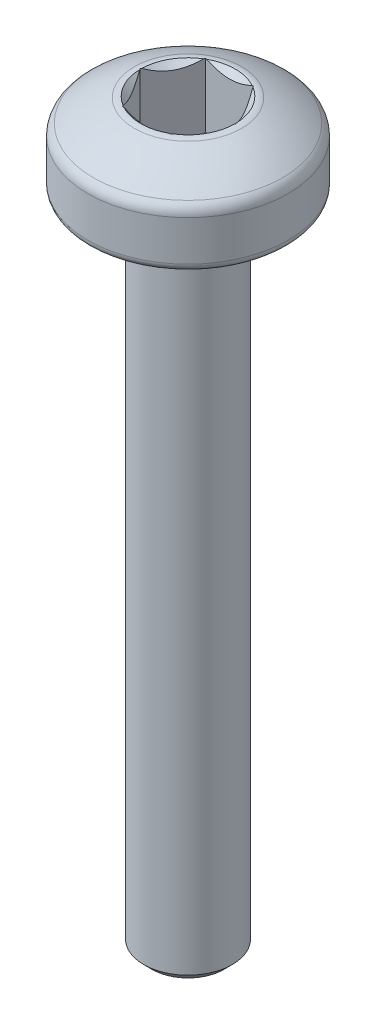
SolidWorks part; units mm, degrees
ref_plane "Front" through (0, 0, 0) normal (0, 0, 1) x (1, 0, 0)
ref_plane "Top" through (0, 0, 0) normal (0, 1, 0) x (1, 0, 0)
ref_plane "Right" through (0, 0, 0) normal (1, 0, 0) x (0, 0, -1)
sketch "Sketch1" plane through (0, 0, 0) normal (1, 0, 0) x (0, 0, -1)
  line L0 (0, 13.5) -> (0, 0) construction
  line L1 (0, 0) -> (7.1673, 0) construction
  line L2 (0, 13.5) -> (-2.498, 13.5) construction
  line L3 (0.95, 11.85) -> (1.66, 11.85)
  line L4 (0.8, 11.7) -> (0.8, 0.15)
  line L5 (0.8, 0.15) -> (0.65, 0)
  line L6 (0.65, 0) -> (0, 0)
  line L7 (0, 0) -> (0, 12)
  line L8 (1.81, 12) -> (1.81, 12.7288)
  line L9 (0.725, 13.22) -> (0.725, 12.2969)
  line L10 (0.725, 13.22) -> (0.855, 13.35)
  line L11 (0.875, 13.3494) -> (0.875, 12.2562)
  arc A0 (0.95, 11.85) -> (0.8, 11.7) centre (0.95, 11.7) ccw
  arc A1 (1.66, 11.85) -> (1.81, 12) centre (1.66, 12) ccw
  arc A2 (0, 12) -> (0.768, 12.1125) centre (0, 14.6781) ccw
  arc A3 (0.725, 12.2969) -> (0.5239, 12.0517) centre (0.475, 12.2969) cw
  arc A4 (0.768, 12.1125) -> (0.875, 12.2562) centre (0.725, 12.2562) ccw
  arc A5 (1.7103, 12.9286) -> (0.9685, 13.3301) centre (0, 10.6549) ccw
  arc A6 (0.855, 13.35) -> (0.9685, 13.3301) centre (0.855, 13.0167) cw
  arc A7 (1.81, 12.7288) -> (1.7103, 12.9286) centre (1.56, 12.7288) ccw
  point P20 (0.725, 12.1)
  point P31 (1.81, 12.85)
  dimension "D5" = 0.15
  dimension "D11" = 0.25
  dimension "D16" = 1
  dimension "D1" = 1.6
  dimension "D2" = 45
  dimension "D3" = 0.15
  dimension "D4" = 11.85
  dimension "D6" = 1.65
  dimension "D7" = 1.5
  dimension "D8" = 3.62
  dimension "D9" = 1.45
  dimension "D10" = 0.25
  dimension "D12" = 45
  dimension "D13" = 0.13
  dimension "D14" = 1.5
  dimension "D15" = 1.75
revolve "Revolve1" add sketch "Sketch1" angle 360 about L0 region at (0, 6.7611, -0.5022)
cosmetic thread "Cosmetic Thread1" parameters "D2"=1.202
revolve "Revolve2" add sketch "Sketch1<3>" angle 360 about L0 region at (0, 12.6908, -0.7953)
sketch "Sketch1<3>" plane through (0, 0, 0) normal (1, 0, 0) x (0, 0, -1) same geometry as "Sketch1"
sketch "Sketch2" plane through (0, 11.85, 0) normal (0, -1, 0) x (1, 0, 0)
  line L1 (-0.433, 0.75) -> (-0.866, 0)
  line L2 (-0.866, 0) -> (-0.433, -0.75)
  line L3 (-0.433, -0.75) -> (0.433, -0.75)
  line L4 (0.433, -0.75) -> (0.866, 0)
  line L5 (0.866, 0) -> (0.433, 0.75)
  line L6 (0.433, 0.75) -> (-0.433, 0.75)
  circle A0 centre (0, 0) radius 0.75 construction
  dimension "D1" = 1.5
extrude "Cut-Extrude2" cut sketch "Sketch2" against normal through all
combine bodies "Combine1" operation type add bodies to combine 101 103
